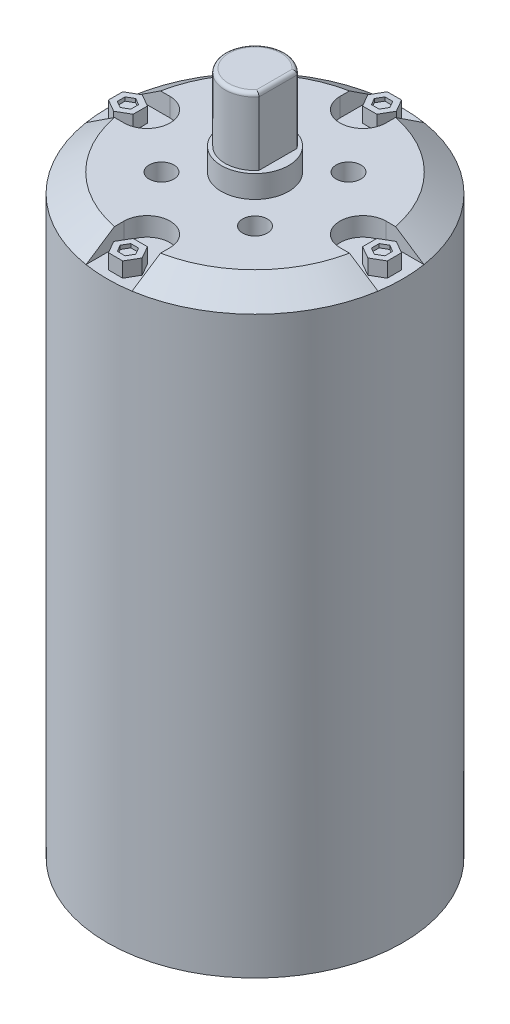
SolidWorks part; units mm, degrees
note: The reader was unsure of these and kept them because the rebuilt part matched: shared geometry of "Sketch4<5>", "Sketch4<7>", "Sketch9<3>".
ref_plane "Front Plane" through (0, 0, 0) normal (0, 0, 1) x (1, 0, 0)
ref_plane "Top Plane" through (0, 0, 0) normal (0, 1, 0) x (1, 0, 0)
ref_plane "Right Plane" through (0, 0, 0) normal (1, 0, 0) x (0, 0, -1)
sketch "Sketch1" plane through (0, 0, 0) normal (0, 1, 0) x (1, 0, 0)
  circle A0 centre (0, 0) radius 39.5
extrude "Boss-Extrude1" add sketch "Sketch1" along normal blind 153.67
sketch "Sketch2" plane through (0, 0, 0) normal (0, 0, 1) x (1, 0, 0)
  line L0 (0, 153.67) -> (-39.5, 153.67)
  line L1 (39.5, 153.67) -> (-39.5, 153.67) construction
  line L3 (-39.5, 153.67) -> (-32, 158.67)
  line L4 (-32, 158.67) -> (0, 158.67)
  line L5 (0, 158.67) -> (0, 153.67)
ref_axis "Axis2" through (0, 158.67, 0) along (0, -1, 0)
revolve "Revolve1" add sketch "Sketch2" angle 360 about axis through (0, 158.67, 0) along (0, -1, 0)
sketch "Sketch4" plane through (0, 158.67, 0) normal (0, 1, 0) x (1, 0, 0)
  line L0 (0, -43.45) -> (0, 43.45) construction
  line L2 (-43.45, 0) -> (43.45, 0) construction
  line L3 (-39.0178, 6.1529) -> (-28.8585, 6.1529)
  line L4 (-39.0178, -6.1529) -> (-28.8585, -6.1529)
  line L5 (-6.1529, 39.0178) -> (-6.1529, 28.8585)
  line L6 (6.1529, 39.0178) -> (6.1529, 28.8585)
  line L7 (39.0178, 6.1529) -> (28.8585, 6.1529)
  line L8 (39.0178, -6.1529) -> (28.8585, -6.1529)
  line L9 (6.1529, -39.0178) -> (6.1529, -28.8585)
  line L10 (-6.1529, -39.0178) -> (-6.1529, -28.8585)
  circle A0 centre (0, 0) radius 9
  circle A1 centre (12.5, 12.5) radius 3.3
  circle A2 centre (-12.5, 12.5) radius 3.3
  circle A3 centre (12.5, -12.5) radius 3.3
  circle A4 centre (-12.5, -12.5) radius 3.3
  circle A5 centre (0, 0) radius 39.5 construction
  arc A6 (-28.8585, 6.1529) -> (-28.8585, -6.1529) centre (-28.8585, 0) cw
  arc A7 (-39.0178, 6.1529) -> (-39.0178, -6.1529) centre (0, 0) ccw
  arc A9 (6.1529, 39.0178) -> (-6.1529, 39.0178) centre (0, 0) ccw
  arc A10 (6.1529, 28.8585) -> (-6.1529, 28.8585) centre (0, 28.8585) cw
  arc A12 (39.0178, -6.1529) -> (39.0178, 6.1529) centre (0, 0) ccw
  arc A13 (28.8585, -6.1529) -> (28.8585, 6.1529) centre (28.8585, 0) cw
  arc A15 (-6.1529, -39.0178) -> (6.1529, -39.0178) centre (0, 0) ccw
  arc A16 (-6.1529, -28.8585) -> (6.1529, -28.8585) centre (0, -28.8585) cw
  point P4 (0, 0.0704)
  point P26 (0, 0)
  point P27 (0, 0)
  point P28 (0, 0)
  dimension "D1" = 4
extrude "Cut-Extrude1" cut sketch "Sketch4" against normal blind 5 contours L8 A13 L7 A12 | A10 L5 A9 L6 | A6 L4 A7 L3 | A16 L9 A15 L10
extrude "Boss-Extrude2" add sketch "Sketch4<5>" along normal blind 6 contours A0
sketch "Sketch4<5>" plane through (0, 158.67, 0) normal (0, 1, 0) x (1, 0, 0) same geometry as "Sketch4"
sketch "Sketch5" plane through (0, 164.67, 0) normal (0, 1, 0) x (1, 0, 0)
  line L1 (6.1565, 5.1085) -> (6.1565, -5.1085)
  arc A1 (6.1565, 5.1085) -> (6.1565, -5.1085) centre (0, 0) ccw
  circle M2 centre (0, 0) radius 9
extrude "Boss-Extrude3" add sketch "Sketch5" along normal blind 18 contours L1 M2
extrude "Cut-Extrude3" cut sketch "Sketch4<7>" against normal blind 17 contours A1 | A2 | A3 | A4
sketch "Sketch4<7>" plane through (0, 158.67, 0) normal (0, 1, 0) x (1, 0, 0) same geometry as "Sketch4"
sketch "Sketch6" plane through (0, 153.67, 0) normal (0, 1, 0) x (1, 0, 0)
  line L0 (-0.1371, -34.1992) -> (0, -33.9618)
  line L1 (1.9053, -30.6618) -> (-1.9053, -30.6618)
  line L5 (3.8105, -33.9618) -> (1.9053, -30.6618)
  line L8 (1.9053, -37.2618) -> (3.8105, -33.9618)
  line L10 (0, -33.9618) -> (-0.1371, -34.1992)
  line L11 (-1.9053, -37.2618) -> (1.9053, -37.2618)
  line L12 (-0.1371, -34.1992) -> (0, -33.9618)
  line L14 (-3.8105, -33.9618) -> (-1.9053, -37.2618)
  line L17 (-1.9053, -30.6618) -> (-3.8105, -33.9618)
  line L19 (0, -33.9618) -> (1.9053, -37.2618) [skipped]
  line L21 (0, -33.9618) -> (-3.8105, -33.9618) [skipped]
  line L22 (0, -33.9618) -> (-1.9053, -30.6618) [skipped]
  line L23 (0, -33.9618) -> (3.8105, -33.9618) [skipped]
  line L24 (-37.2618, 1.9053) -> (-37.2618, -1.9053)
  line L25 (-37.2618, -1.9053) -> (-33.9618, -3.8105)
  line L26 (-33.9618, -3.8105) -> (-30.6618, -1.9053)
  line L27 (-30.6618, -1.9053) -> (-30.6618, 1.9053)
  line L28 (-30.6618, 1.9053) -> (-33.9618, 3.8105)
  line L29 (-33.9618, 3.8105) -> (-37.2618, 1.9053)
  line L30 (1.9053, 37.2618) -> (-1.9053, 37.2618)
  line L31 (-1.9053, 37.2618) -> (-3.8105, 33.9618)
  line L32 (-3.8105, 33.9618) -> (-1.9053, 30.6618)
  line L33 (-1.9053, 30.6618) -> (1.9053, 30.6618)
  line L34 (1.9053, 30.6618) -> (3.8105, 33.9618)
  line L35 (3.8105, 33.9618) -> (1.9053, 37.2618)
  line L36 (37.2618, -1.9053) -> (37.2618, 1.9053)
  line L37 (37.2618, 1.9053) -> (33.9618, 3.8105)
  line L38 (33.9618, 3.8105) -> (30.6618, 1.9053)
  line L39 (30.6618, 1.9053) -> (30.6618, -1.9053)
  line L40 (30.6618, -1.9053) -> (33.9618, -3.8105)
  line L41 (33.9618, -3.8105) -> (37.2618, -1.9053)
  dimension "D1" = 3.3
  dimension "D2" = 6
  dimension "D3" = 4
extrude "Boss-Extrude4" add sketch "Sketch6" along normal blind 4
sketch "Sketch8" plane through (0, 157.67, 0) normal (0, 1, 0) x (1, 0, 0)
  line L16 (-35.7618, 1.0392) -> (-35.7618, -1.0392)
  line L17 (-35.7618, -1.0392) -> (-33.9618, -2.0785)
  line L18 (-33.9618, -2.0785) -> (-32.1618, -1.0392)
  line L19 (-32.1618, -1.0392) -> (-32.1618, 1.0392)
  line L20 (-32.1618, 1.0392) -> (-33.9618, 2.0785)
  line L21 (-33.9618, 2.0785) -> (-35.7618, 1.0392)
  line L22 (-1.0392, -35.7618) -> (1.0392, -35.7618)
  line L23 (-2.0785, -33.9618) -> (-1.0392, -35.7618)
  line L24 (-1.0392, -32.1618) -> (-2.0785, -33.9618)
  line L25 (1.0392, -32.1618) -> (-1.0392, -32.1618)
  line L26 (2.0785, -33.9618) -> (1.0392, -32.1618)
  line L27 (1.0392, -35.7618) -> (2.0785, -33.9618)
  line L28 (-1.0392, -35.7618) -> (1.0392, -35.7618)
  line L29 (-2.0785, -33.9618) -> (-1.0392, -35.7618)
  line L30 (-1.0392, -32.1618) -> (-2.0785, -33.9618)
  line L31 (1.0392, -32.1618) -> (-1.0392, -32.1618)
  line L32 (2.0785, -33.9618) -> (1.0392, -32.1618)
  line L33 (1.0392, -35.7618) -> (2.0785, -33.9618)
  line L34 (1.0392, 35.7618) -> (-1.0392, 35.7618)
  line L35 (-1.0392, 35.7618) -> (-2.0785, 33.9618)
  line L36 (-2.0785, 33.9618) -> (-1.0392, 32.1618)
  line L37 (-1.0392, 32.1618) -> (1.0392, 32.1618)
  line L38 (1.0392, 32.1618) -> (2.0785, 33.9618)
  line L39 (2.0785, 33.9618) -> (1.0392, 35.7618)
  line L40 (35.7618, -1.0392) -> (35.7618, 1.0392)
  line L41 (35.7618, 1.0392) -> (33.9618, 2.0785)
  line L42 (33.9618, 2.0785) -> (32.1618, 1.0392)
  line L43 (32.1618, 1.0392) -> (32.1618, -1.0392)
  line L44 (32.1618, -1.0392) -> (33.9618, -2.0785)
  line L45 (33.9618, -2.0785) -> (35.7618, -1.0392)
  dimension "D1" = 1.5
  dimension "D2" = 4
extrude "Cut-Extrude5" cut sketch "Sketch8" against normal blind 1 contours L32 L31 L30 L29 L28 L33 | L43 L44 L45 L40 L41 L42 | L20 L21 L16 L17 L18 L19 | L38 L39 L34 L35 L36 L37
sketch "Sketch9" plane through (0, 0, 0) normal (0, -1, 0) x (1, 0, 0)
  circle A0 centre (0, 0) radius 10.6651
  circle A1 centre (22.4009, -0.0764) radius 6.043
extrude "Cut-Extrude6" cut sketch "Sketch9" against normal blind 10 contours A1
pattern_circular "CirPattern1" count 8 every 45 about axis through (-0.5369, 0, 0.0018) along (0, 1, 0) of "Cut-Extrude6"
extrude "Cut-Extrude7" cut sketch "Sketch9<3>" against normal blind 10 contours A0
sketch "Sketch9<3>" plane through (0, 0, 0) normal (0, -1, 0) x (1, 0, 0) same geometry as "Sketch9"
sketch "Sketch10" plane through (0, 10, 0) normal (0, -1, 0) x (1, 0, 0)
  circle A0 centre (0, 0) radius 8
extrude "Boss-Extrude5" add sketch "Sketch10" along normal blind 9
fillet "Fillet3" radius 0.5 1 edges at (0, 1, -8)
fillet "Fillet4" radius 1 2 edges at (-8, 182.67, 0) (6.1565, 182.67, 0)
